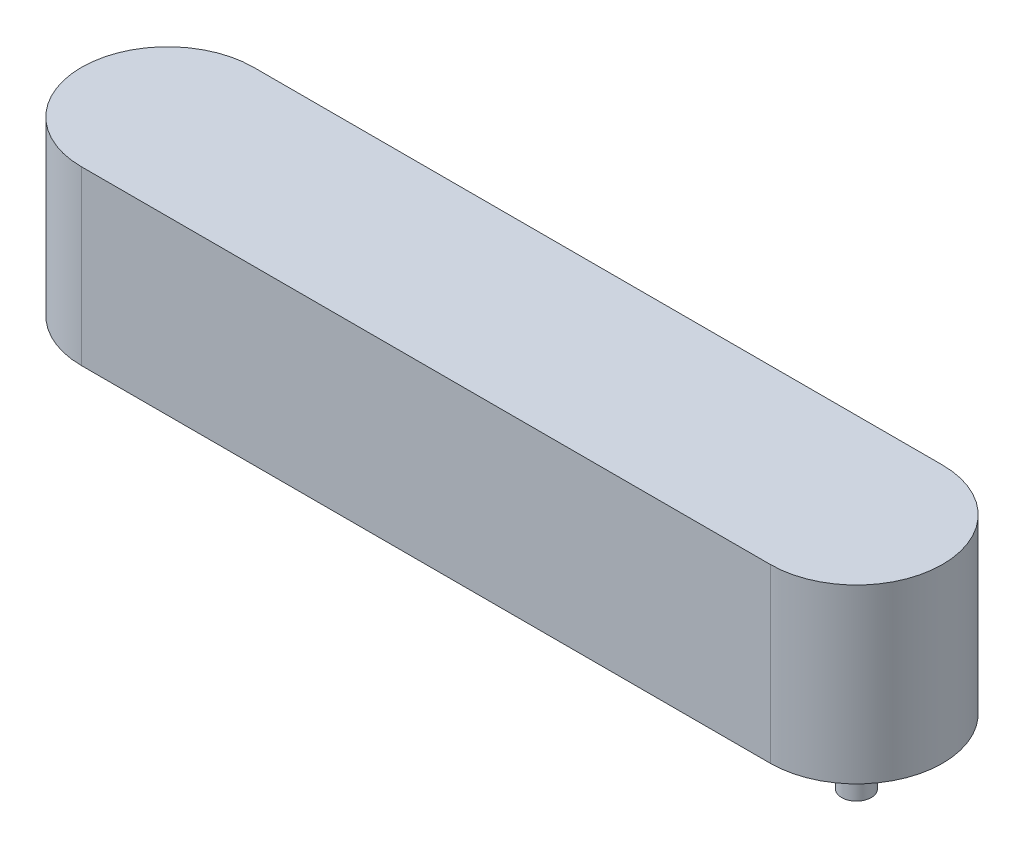
SolidWorks part; units mm, degrees
ref_plane "Ebene vorne" through (0, 0, 0) normal (0, 0, 1) x (1, 0, 0)
ref_plane "Ebene oben" through (0, 0, 0) normal (0, 1, 0) x (1, 0, 0)
ref_plane "Ebene rechts" through (0, 0, 0) normal (1, 0, 0) x (0, 0, -1)
sketch "Skizze1" plane through (0, 0, 0) normal (0, 0, 1) x (1, 0, 0)
  line L0 (0, 0) -> (13.5789, 0) construction
  line L1 (0, 0) -> (0, 10.1716) construction
  line L3 (-7.25, 1.45) -> (7.25, 1.45)
  line L4 (-7.25, 1.45) -> (-7.25, -1.45)
  line L5 (-7.25, -1.45) -> (7.25, -1.45)
  line L6 (7.25, 1.45) -> (7.25, -1.45)
  dimension "D1" = 14.5
  dimension "D2" = 2.9
extrude "Aufsatz-Linear austragen1" add sketch "Skizze1" along normal mid plane 2.9
fillet "Verrundung1" 2 edges at (7.25, 0, -1.45) (7.25, 0, 1.45) type full round first side face at (0, 0, -1.45) second side face at (0, 0, 1.45) middle face at (7.25, 0, 0)
fillet "Verrundung2" 2 edges at (-7.25, 0, 1.45) (-7.25, 0, -1.45) type full round first side face at (-0.725, 0, 1.45) second side face at (-0.725, 0, -1.45) middle face at (-7.25, 0, 0)
sketch "Skizze2" plane through (0, -1.45, 0) normal (0, -1, 0) x (1, 0, 0)
  circle A0 centre (-5.8, 0) radius 0.25
  circle A1 centre (5.8, 0) radius 0.25
  dimension "D1" = 0.5
extrude "Aufsatz-Linear austragen2" add sketch "Skizze2" along direction (0, -1, 0) on the side of the normal offset from surface (1.1 mm away) 4 up to face at (0, 1.45, 0)
